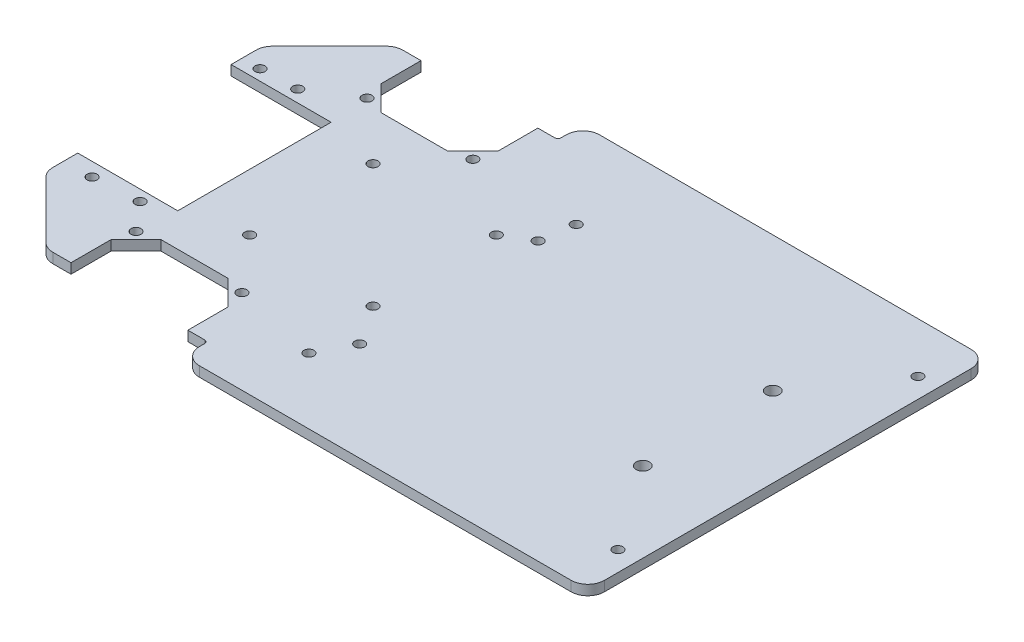
SolidWorks part; units mm, degrees
ref_plane "Front Plane" through (0, 0, 0) normal (0, 0, 1) x (1, 0, 0)
ref_plane "Top Plane" through (0, 0, 0) normal (0, 1, 0) x (1, 0, 0)
ref_plane "Right Plane" through (0, 0, 0) normal (1, 0, 0) x (0, 0, -1)
sketch "Sketch1" plane through (0, 0, 0) normal (0, 1, 0) x (1, 0, 0)
  line L0 (190, 0) -> (0, 0) construction
  line L1 (0, -60) -> (190, -60)
  line L2 (0, -60) -> (0, 60)
  line L3 (0, 60) -> (190, 60)
  line L4 (190, -60) -> (190, 60)
  line L5 (0, -32.5266) -> (27.4734, -60)
  line L6 (30, 23) -> (0, 23) construction
  line L7 (30, 23) -> (30, -23) construction
  line L8 (30, -23) -> (0, -23) construction
  line L9 (0, 23) -> (0, -23)
  line L10 (30, 23) -> (0, -23) construction
  line L11 (30, -23) -> (0, 23) construction
  line L12 (19.9734, -52.5) -> (27.4734, -52.5) construction
  line L13 (68.5266, -52.5) -> (68.5266, -60) construction
  line L14 (35, -33) -> (27.4734, -40.5266) construction
  line L15 (27.4734, -52.5) -> (27.4734, -40.5266) construction
  line L16 (27.4734, -40.5266) -> (27.4734, -52.5) construction
  line L17 (0, 32.5266) -> (27.4734, 60)
  line L18 (35, -33) -> (55, -33) construction
  line L19 (55, -33) -> (62.5266, -40.5266) construction
  line L20 (62.5266, -52.5) -> (68.5266, -52.5) construction
  line L21 (47.5, -37) -> (42.5, -37) construction
  line L22 (45, -37) -> (45, -33) construction
  line L23 (45, -56.5) -> (45, -52.5) construction
  line L24 (39.4, -56.5) -> (50.6, -56.5) construction
  line L25 (27.4734, -52.5) -> (62.5266, -52.5) construction
  line L27 (62.5266, -40.5266) -> (62.5266, -52.5) construction
  point P7 (0, 0)
  point P8 (15, 0)
  dimension "D1" = 120
  dimension "D2" = 190
  dimension "D3" = 30
  dimension "D4" = 23
  dimension "D5" = 10
  dimension "D6" = 20
  dimension "D7" = 45
  dimension "D8" = 45
  dimension "D9" = 45
  dimension "D10" = 7.5
  dimension "D11" = 6
extrude "Boss-Extrude1" add sketch "Sketch1" along normal blind 3 contours L7 L8 L2 L1 L4 L3 L6 region at (97.9391, 0, 0)
sketch "Sketch4" plane through (0, 0, 0) normal (0, 1, 0) x (1, 0, 0)
  line L0 (68.5266, -60) -> (68.5266, -52.5)
  line L1 (68.5266, -52.5) -> (62.5266, -52.5)
  line L2 (62.5266, -52.5) -> (62.5266, -40.5266)
  line L3 (62.5266, -40.5266) -> (55, -33)
  line L4 (55, -33) -> (35, -33)
  line L5 (35, -33) -> (27.4734, -40.5266)
  line L6 (27.4734, -40.5266) -> (27.4734, -52.5)
  line L7 (27.4734, -52.5) -> (19.9734, -52.5)
  line L8 (19.9734, -52.5) -> (27.4734, -60)
  line L9 (27.4734, -60) -> (68.5266, -60)
  line L10 (0, 0) -> (190, 0) construction
  line L11 (190, -60) -> (190, 60) construction
  line L12 (27.4734, 60) -> (68.5266, 60)
  line L13 (19.9734, 52.5) -> (27.4734, 60)
  line L14 (27.4734, 52.5) -> (19.9734, 52.5)
  line L15 (27.4734, 40.5266) -> (27.4734, 52.5)
  line L16 (35, 33) -> (27.4734, 40.5266)
  line L17 (55, 33) -> (35, 33)
  line L18 (62.5266, 40.5266) -> (55, 33)
  line L19 (62.5266, 52.5) -> (62.5266, 40.5266)
  line L20 (68.5266, 52.5) -> (62.5266, 52.5)
  line L21 (68.5266, 60) -> (68.5266, 52.5)
  line L23 (30, 23) -> (0, 23)
  line L24 (30, 23) -> (30, -23)
  line L25 (30, -23) -> (0, -23)
  line L26 (0, 23) -> (0, -23)
extrude "Cut-Extrude1" cut sketch "Sketch4" along normal up to surface (3 mm away) up to face at (72.4911, 3, 0)
fillet "Fillet1" radius 5 8 edges at (19.9734, 1.5, -52.5) (0, 1.5, -32.5266) (68.5266, 1.5, -60) (190, 1.5, -60) (190, 1.5, 60) (0, 1.5, 32.5266) (19.9734, 1.5, 52.5) (68.5266, 1.5, 60)
fillet "Fillet2" radius 1 2 edges at (68.5266, 1.5, -52.5) (68.5266, 1.5, 52.5)
sketch "Sketch5" plane through (0, 0, 0) normal (0, 1, 0) x (1, 0, 0)
  circle A0 centre (47.0626, -18.5) radius 1.5 construction
  circle A1 centre (47.0626, -18.5) radius 1.5
  circle A2 centre (84.0626, -18.5) radius 1.5 construction
  circle A3 centre (84.0626, -18.5) radius 1.5
  circle A4 centre (84.0626, 18.5) radius 1.5 construction
  circle A5 centre (84.0626, 18.5) radius 1.5
  circle A6 centre (47.0626, 18.5) radius 1.5 construction
  circle A7 centre (47.0626, 18.5) radius 1.5
  circle A8 centre (91.88, 23.2195) radius 1.5 construction
  circle A9 centre (91.88, 23.2195) radius 1.5
  circle A10 centre (93.3054, 33.2195) radius 1.5 construction
  circle A11 centre (93.3054, 33.2195) radius 1.5
  circle A12 centre (29.1154, 34.642) radius 1.5 construction
  circle A13 centre (60.8846, 34.642) radius 1.5 construction
  circle A14 centre (8.3674, -27.0854) radius 1.5 construction
  circle A15 centre (16.3794, 26.6064) radius 1.5 construction
  circle A16 centre (91.88, -30.308) radius 1.5 construction
  circle A17 centre (86.6598, -40.308) radius 1.5 construction
  circle A18 centre (29.1154, 34.642) radius 1.5
  circle A19 centre (60.8846, 34.642) radius 1.5
  circle A20 centre (8.3674, -27.0854) radius 1.5
  circle A21 centre (16.3794, 26.6064) radius 1.5
  circle A22 centre (91.88, -30.308) radius 1.5
  circle A23 centre (86.6598, -40.308) radius 1.5
  circle A24 centre (184.0458, -45) radius 1.5 construction
  circle A25 centre (184.0458, 45) radius 1.5 construction
  circle A26 centre (184.0458, -45) radius 1.5
  circle A27 centre (184.0458, 45) radius 1.5
  circle A28 centre (166, -19.5) radius 2 construction
  circle A29 centre (166, 19.5) radius 2 construction
  circle A30 centre (166, -19.5) radius 2
  circle A31 centre (166, 19.5) radius 2
  circle A32 centre (29.1154, -34.642) radius 1.5 construction
  circle A33 centre (60.8846, -34.642) radius 1.5 construction
  circle A34 centre (29.1154, -34.642) radius 1.5
  circle A35 centre (60.8846, -34.642) radius 1.5
  circle A36 centre (21.9337, -26.25) radius 1.5 construction
  circle A37 centre (5.4397, 26.25) radius 1.5 construction
  circle A38 centre (21.9337, -26.25) radius 1.5
  circle A39 centre (5.4397, 26.25) radius 1.5
extrude "Cut-Extrude2" cut sketch "Sketch5" along normal up to surface (3 mm away) up to face at (55.2686, 3, 0)
